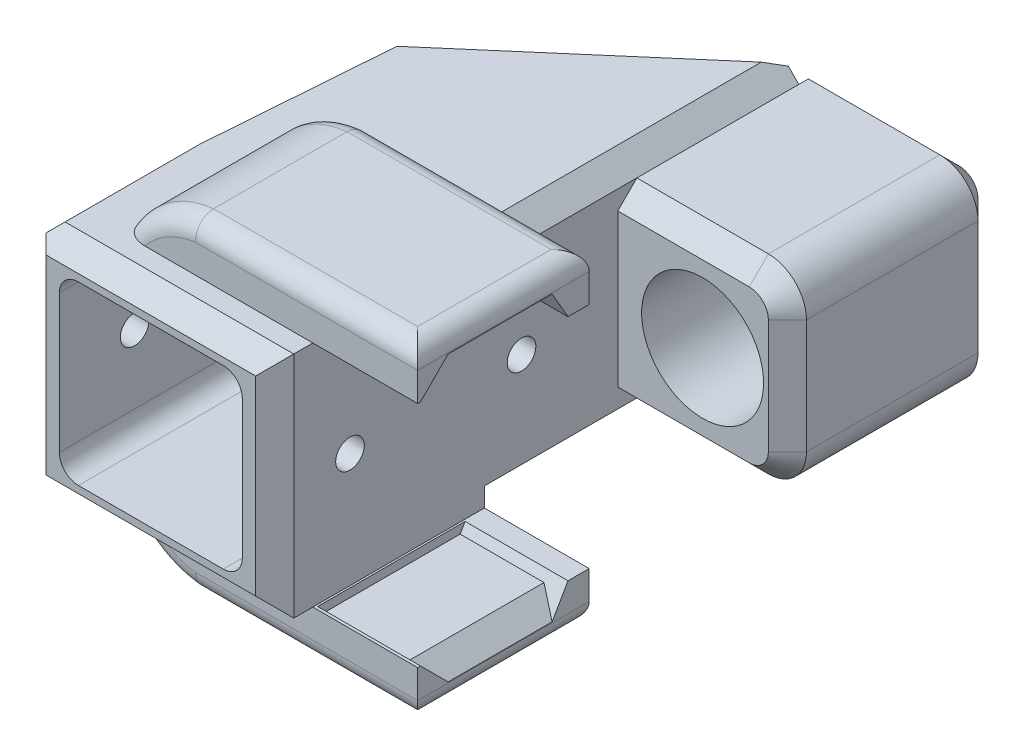
SolidWorks part; units mm, degrees
material "ABS"
ref_plane "Front Plane" through (0, 0, 0) normal (0, 0, 1) x (1, 0, 0)
ref_plane "Top Plane" through (0, 0, 0) normal (0, 1, 0) x (1, 0, 0)
ref_plane "Right Plane" through (0, 0, 0) normal (1, 0, 0) x (0, 0, -1)
sketch "Sketch2" plane through (0, 0, 0) normal (0, 0, 1) x (1, 0, 0)
  line L0 (-3.5, 6) -> (-3.5, 8.5)
  line L1 (-6.5, 6) -> (6.5, 6)
  line L2 (-6.5, 6) -> (-6.5, -6)
  line L3 (-6.5, -6) -> (6.5, -6)
  line L4 (6.5, 6) -> (6.5, -6)
  line L5 (-6.5, 6) -> (6.5, -6) construction
  line L6 (-6.5, -6) -> (6.5, 6) construction
  line L7 (-3.5, 8.5) -> (12, 8.5)
  line L8 (12, 8.5) -> (12, 6)
  line L9 (12, 6) -> (6.5, 6)
  line L10 (-6.5, 0) -> (6.5, 0) construction
  line L11 (12, -8.5) -> (12, -6)
  line L12 (-3.5, -8.5) -> (12, -8.5)
  line L13 (12, -6) -> (6.5, -6)
  line L14 (-3.5, -6) -> (-3.5, -8.5)
  point P0 (0, 0)
  dimension "D1" = 13
  dimension "D2" = 12
  dimension "D3" = 3.5
  dimension "D4" = 2.5
  dimension "D5" = 15.5
extrude "Boss-Extrude3" add sketch "Sketch2" against normal blind 29 contours L9 L8 L7 L0 L1 | L4 L1 L2 L3 | L3 L14 L12 L11 L13
sketch "Sketch4" plane through (0, 0, 0) normal (0, 0, 1) x (1, 0, 0)
  line L1 (-3.8, -4.625) -> (3.8, -4.625)
  line L2 (-4.8, -3.625) -> (-4.8, 3.625)
  line L3 (-3.8, 4.625) -> (3.8, 4.625)
  line L4 (4.8, -3.625) -> (4.8, 3.625)
  line L5 (-4.8, -4.625) -> (4.8, 4.625) construction
  line L6 (-4.8, 4.625) -> (4.8, -4.625) construction
  arc A0 (4.8, -3.625) -> (3.8, -4.625) centre (3.8, -3.625) cw
  arc A1 (4.8, 3.625) -> (3.8, 4.625) centre (3.8, 3.625) ccw
  arc A2 (-3.8, -4.625) -> (-4.8, -3.625) centre (-3.8, -3.625) cw
  arc A3 (-3.8, 4.625) -> (-4.8, 3.625) centre (-3.8, 3.625) ccw
  point P0 (0, 0)
  dimension "D3" = 1
  dimension "D1" = 9.6
  dimension "D2" = 9.25
extrude "Cut-Extrude2" cut sketch "Sketch4" against normal blind 17.2
sketch "Sketch5" plane through (0, 0, 0) normal (0, 0, 1) x (1, 0, 0)
  line L0 (-3.5, 6) -> (12, 6)
  line L1 (12, 6) -> (12, 8.5)
  line L2 (12, 8.5) -> (-3.5, 8.5)
  line L3 (-3.5, 8.5) -> (-3.5, 6)
  line L4 (-3.5, -6) -> (-3.5, -8.5)
  line L5 (-3.5, -8.5) -> (12, -8.5)
  line L6 (12, -8.5) -> (12, -6)
  line L7 (12, -6) -> (-3.5, -6)
extrude "Cut-Extrude3" cut sketch "Sketch5" against normal blind 2
sketch "Sketch6" plane through (0, 8.5, 0) normal (0, 1, 0) x (1, 0, 0)
  line L0 (12, 29) -> (12, 11)
  line L1 (12, 29) -> (12, 2) construction
  line L2 (12, 11) -> (-3.5, 11)
  line L3 (-3.5, 29) -> (-3.5, 2) construction
  line L4 (-3.5, 11) -> (-3.5, 29)
  line L5 (-6.5, 29) -> (-3.5, 29) construction
  line L6 (-3.5, 29) -> (12, 29)
  dimension "D1" = 18
fillet "Chamfer4" radius 1 4 edges at (6.5, 0, 0) (0, -6, 0) (-6.5, 0, 0) (0, 6, 0) profile chamfer
extrude "Cut-Extrude4" cut sketch "Sketch6" against normal blind 2.5
sketch "Sketch8" plane through (0, -8.5, 0) normal (0, -1, 0) x (1, 0, 0)
  line L0 (12, -29) -> (12, -11)
  line L1 (12, -29) -> (12, -2) construction
  line L2 (12, -11) -> (-3.5, -11)
  line L3 (-3.5, -29) -> (-3.5, -2) construction
  line L4 (-3.5, -11) -> (-3.5, -29)
  line L5 (-3.5, -29) -> (12, -29)
  dimension "D1" = 18
extrude "Cut-Extrude5" cut sketch "Sketch8" against normal blind 2.5
sketch "Sketch9" plane through (6.5, 0, 0) normal (1, 0, 0) x (0, 0, -1)
  line L7 (0, 0) -> (29, 0) construction
  line L8 (29, 6) -> (29, -6) construction
  line L9 (18, 0) -> (18, 5)
  line L10 (18, 5) -> (29, 5)
  line L12 (29, -5) -> (18, -5)
  line L13 (18, -5) -> (18, 0)
  line L14 (29, 5) -> (29, -5)
  dimension "D1" = 10
  dimension "D2" = 11
extrude "Boss-Extrude4" add sketch "Sketch9" along normal blind 8.9
sketch "Sketch10" plane through (0, 0, -18) normal (0, 0, 1) x (1, 0, 0)
  line L0 (6.5, 5) -> (15.4, -5) construction
  line L1 (15.4, 5) -> (6.5, -5) construction
  circle A0 centre (10.95, 0) radius 3.2
  dimension "D1" = 6.4
extrude "Cut-Extrude6" cut sketch "Sketch10" against normal blind 11
sketch "Sketch11" plane through (0, 0, -29) normal (0, 0, -1) x (-1, 0, 0)
  line L0 (-6.5, 6) -> (-6.5, -6)
  line L1 (-6.5, -6) -> (6.5, -6)
  line L2 (6.5, 6) -> (6.5, -6) construction
  line L3 (6.5, -6) -> (-6.5, -6) construction
  line L4 (6.5, -6) -> (6.5, 6)
  line L5 (6.5, 6) -> (-6.5, 6)
extrude "Cut-Extrude7" cut sketch "Sketch11" against normal blind 1.5
fillet "Fillet1" radius 2 2 edges at (15.4, 5, -23.5) (15.4, -5, -23.5)
chamfer "Chamfer5" distance 1 angle 45 11 edges at (15.4, 0, -18) (9.95, -5, -18) (9.95, 5, -18) (9.95, 5, -29) (6.5, 0, -29) (9.95, -5, -29) (15.4, 0, -29) (14.8142, -4.4142, -18) (14.8142, -4.4142, -29) (14.8142, 4.4142, -29) (14.8142, 4.4142, -18)
sketch "Sketch14" plane through (0, 6, 0) normal (0, 1, 0) x (1, 0, 0)
  line L0 (-6.5, 27.5) -> (-6.5, 17.5235)
  line L1 (-6.5, 27.5) -> (-6.5, 1) construction
  line L2 (-6.5, 17.5235) -> (5.1, 27.5)
  line L3 (-6.5, 27.5) -> (6.5, 27.5) construction
  line L4 (5.1, 27.5) -> (-6.5, 27.5)
  dimension "D1" = 1.4
  dimension "D2" = 15.3
extrude "Cut-Extrude9" cut sketch "Sketch14" against normal through all
chamfer "Chamfer6" distance 1 angle 45 5 edges at (5.8, -6, -27.5) (5.8, 6, -27.5) (-0.7, -6, -22.5118) (-6.5, 0, -17.5235) (-0.7, 6, -22.5118)
sketch "Sketch16" plane through (0, 0, -2) normal (0, 0, 1) x (1, 0, 0)
  line L2 (1.4, 8.5) -> (-3.5, 8.5)
  line L3 (-3.5, 8.5) -> (-3.5, 6)
  line L5 (16.3912, 0) -> (-7.8007, 0) construction
  line L7 (12, 8.5) -> (-3.5, 8.5) construction
  line L8 (-3.5, 6) -> (1.4, 6)
  line L11 (1.4, 6) -> (1.4, 8.5)
  line L12 (1.4, -8.5) -> (-3.5, -8.5)
  line L13 (-3.5, -8.5) -> (-3.5, -6)
  line L14 (1.4, -8.5) -> (1.5, -6)
  line L15 (6.5, -6) -> (-3.5, -6) construction
  line L16 (1.5, -6) -> (-3.5, -6)
  arc A0 (-3.5, 6) -> (1.4, 8.5) centre (0.8477, 3.5306) cw
  arc A1 (-3.5, -6) -> (1.4, -8.5) centre (0.8477, -3.5306) ccw
  line M8 (-3.5, 8.5) -> (-3.5, 6)
  dimension "D1" = 5
  dimension "D2" = 4.9
extrude "Cut-Extrude11" cut sketch "Sketch16" against normal blind 11.5 contours A1 L13 L12 | A0 L2 M8
chamfer "Chamfer7" distance 1 angle 45 12 edges at (6.5, -5.4564, -27.5) (6.5, -6, -19.1925) (-6.5, -6, -4.5498) (-6.174, -6, -12.4325) (6.5, 5.4564, -27.5) (6.5, 6, -19.1925) (6.5, 5.9564, -27.4425) (6.5, -5.9564, -27.4425) (-6.5, 6, -4.5498) (-6.174, 6, -12.4325) (-5.7949, 5.5, -17.4705) (-5.7949, -5.5, -17.4705)
fillet "Fillet2" radius 1 10 edges at (12, 8.5, -6.5) (12, -8.5, -6.5) (-1.9028, 7.7061, -11) (6.1477, 8.5, -11) (6.1477, 8.5, -2) (-1.9028, 7.7061, -2) (-1.9028, -7.7061, -11) (-1.9028, -7.7061, -2) (6.1477, -8.5, -11) (6.1477, -8.5, -2)
sketch "Sketch17" plane through (6.5, 0, 0) normal (1, 0, 0) x (0, 0, -1)
  line L0 (18, 0) -> (13.7, 0) construction
  line L1 (18, -3) -> (18, 3) construction
  line L2 (13.7, 0) -> (12.2, 0) construction
  line L3 (12.2, 0) -> (4.7, 0) construction
  line L4 (4.7, 0) -> (3.2, 0) construction
  circle A0 centre (3.95, 0) radius 0.75
  circle A1 centre (12.95, 0) radius 0.75
  dimension "D2" = 1.5
  dimension "D1" = 4.3
  dimension "D3" = 7.5
  dimension "D4" = 1.5
extrude "Cut-Extrude12" cut sketch "Sketch17" against normal through all and the other way through all contours A0 | A1
sketch "Sketch18" plane through (4.8, 0, 0) normal (-1, 0, 0) x (0, 0, 1)
  circle A0 centre (-12.95, 0) radius 0.7951
  circle A1 centre (-3.95, 0) radius 0.75
extrude "Boss-Extrude5" add sketch "Sketch18" against normal blind 0.2
ref_plane "Plane1" through (0, 0, 0) normal (0, -1, 0) x (-1, 0, 0)
sketch "Sketch19" plane through (0, 0, 0) normal (0, -1, 0) x (-1, 0, 0)
  line L1 (-12, 11) -> (-12, 2) construction
  line L2 (-12, 9.6) -> (-6.6, 9.6)
  line L3 (-6.6, 9.6) -> (-6.6, 2.9)
  line L4 (-6.6, 2.9) -> (-12, 2.9)
  line L5 (-12, 2.9) -> (-12, 9.6)
  dimension "D2" = 5.4
  dimension "D3" = 6.7
extrude "Cut-Extrude13" cut sketch "Sketch19" against normal mid plane 12.9
chamfer "Chamfer8" distance 0.75 angle 45 2 edges at (9.3, -6, -2.9) (9.3, 6, -2.9)
chamfer "Chamfer9" distance 0.5 angle 30 2 edges at (9.3, -6, -9.6) (9.3, 6, -9.6)
chamfer "Chamfer10" distance 1 angle 45 2 edges at (12, -6.45, -6.1144) (12, 6.45, -6.1144)
